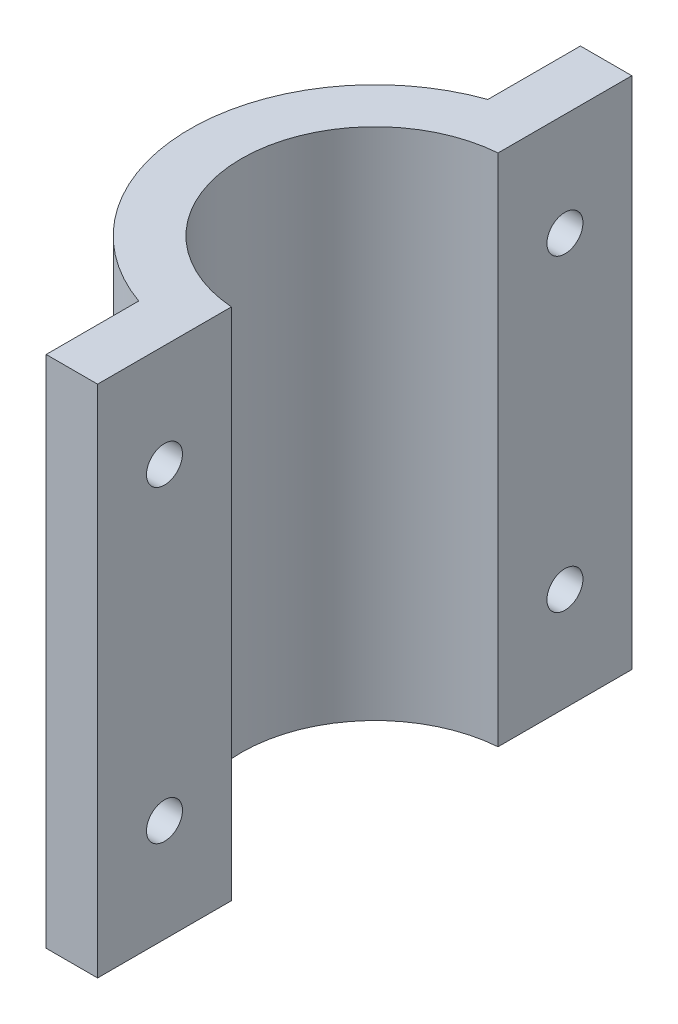
SolidWorks part; units mm, degrees
ref_plane "Front Plane" through (0, 0, 0) normal (0, 0, 1) x (1, 0, 0)
ref_plane "Top Plane" through (0, 0, 0) normal (0, 1, 0) x (1, 0, 0)
ref_plane "Right Plane" through (0, 0, 0) normal (1, 0, 0) x (0, 0, -1)
sketch "Sketch6" plane through (0, 0, 0) normal (0, -1, 0) x (1, 0, 0)
  line L5 (-1, 25.9706) -> (-1, 12.9615)
  line L6 (-1, 25.9706) -> (-6, 25.9706)
  line L7 (-6, 25.9706) -> (-6, 16.9706)
  line L8 (-6, -16.9706) -> (-6, -25.9706)
  line L9 (-6, -25.9706) -> (-1, -25.9706)
  line L10 (-1, -25.9706) -> (-1, -12.9615)
  line L11 (-13, 0) -> (-18, 0) construction
  arc A0 (-1, 12.9615) -> (-1, -12.9615) centre (0, 0) ccw
  arc A1 (-6, 16.9706) -> (-6, -16.9706) centre (0, 0) ccw
  point P0 (0, 0)
  point P7 (-4.0669, -12.2854)
  dimension "D1" = 26
  dimension "D2" = 5
  dimension "D3" = 1
  dimension "D4" = 9
extrude "Boss-Extrude4" add sketch "Sketch6" along normal blind 50
sketch "Sketch7" plane through (-1, 0, 0) normal (1, 0, 0) x (0, 0, -1)
  line L0 (-19.466, -50) -> (-19.466, 0) construction
  line L3 (0, 0) -> (0, -50) construction
  line L6 (-25.9706, -25) -> (25.9706, -25) construction
  line L11 (-12.9615, 0) -> (-25.9706, 0) construction
  line L12 (-12.9615, -50) -> (-25.9706, -50) construction
  line L13 (-25.9706, -50) -> (-25.9706, 0) construction
  line L14 (25.9706, -50) -> (25.9706, 0) construction
  line L15 (-12.9615, -50) -> (12.9615, -50) construction
  circle A0 centre (-19.466, -10) radius 1.75
  circle A1 centre (-19.466, -40) radius 1.75
  circle A2 centre (19.466, -40) radius 1.75
  circle A3 centre (19.466, -10) radius 1.75
  point P4 (-19.466, 0)
  point P6 (10.034, -44.5824)
  point P7 (10.034, -6.8761)
  point P11 (29.5, 0)
  point P13 (-19.466, -50)
  point P17 (-25.9706, -25)
  point P26 (25.9706, -25)
  point P27 (10.034, 0)
  point P30 (10.034, 17.3153)
  point P31 (0, -50)
  point P34 (0, 0)
  dimension "D1" = 10
  dimension "D2" = 3.5
extrude "Cut-Extrude1" cut sketch "Sketch7" against normal through all
